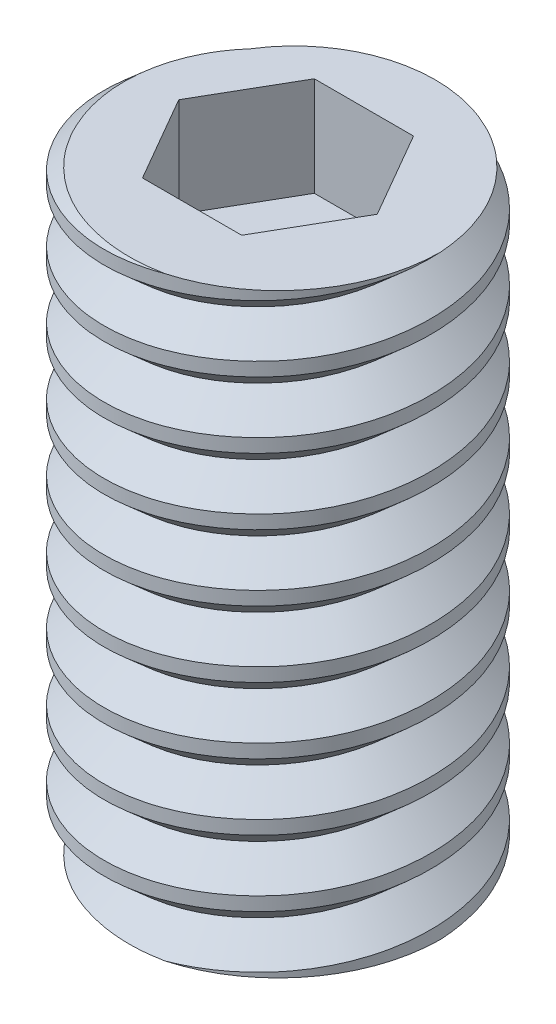
SolidWorks part; units mm, degrees
ref_plane "Front Plane" through (0, 0, 0) normal (0, 0, 1) x (1, 0, 0)
ref_plane "Top Plane" through (0, 0, 0) normal (0, 1, 0) x (1, 0, 0)
ref_plane "Right Plane" through (0, 0, 0) normal (1, 0, 0) x (0, 0, -1)
sketch "Sketch1" plane through (0, 0, 0) normal (0, 1, 0) x (1, 0, 0)
  circle A0 centre (0, 0) radius 1.65
  dimension "D1" = 3.3
extrude "Boss-Extrude1" add sketch "Sketch1" along normal blind 6
sketch "Sketch2" plane through (0, 0, 0) normal (0, 0, 1) x (1, 0, 0)
  line L0 (1.65, 6) -> (1.35, 5.7354)
  line L1 (1.35, 5.7354) -> (1.65, 5.4708)
  line L2 (1.65, 0) -> (1.65, 6) construction
  line L3 (1.65, 6) -> (1.65, 5.4708)
  dimension "D1" = 0.4
  dimension "D2" = 0.3
ref_plane "Plane1" through (0, 6.5, 0) normal (0, 1, 0) x (1, 0, 0)
sketch "Sketch5" plane through (0, 6.5, 0) normal (0, 1, 0) x (1, 0, 0)
  circle A0 centre (0, 0) radius 1.65
  circle A1 centre (0, 0) radius 1.65 construction
curve "Helix/Spiral2" pitch 0.6667 height 10 turns 15
sweep "Cut-Sweep2" cut profiles "Sketch2" path "Helix/Spiral2"
sketch "Sketch6" plane through (0, 6, 0) normal (0, 1, 0) x (1, 0, 0)
  line L1 (1, 0) -> (0.5, 0.866)
  line L2 (0.5, 0.866) -> (-0.5, 0.866)
  line L3 (-0.5, 0.866) -> (-1, 0)
  line L4 (-1, 0) -> (-0.5, -0.866)
  line L5 (-0.5, -0.866) -> (0.5, -0.866)
  line L6 (0.5, -0.866) -> (1, 0)
  circle A0 centre (0, 0) radius 0.866 construction
  dimension "D1" = 1
extrude "Cut-Extrude1" cut sketch "Sketch6" against normal blind 1
